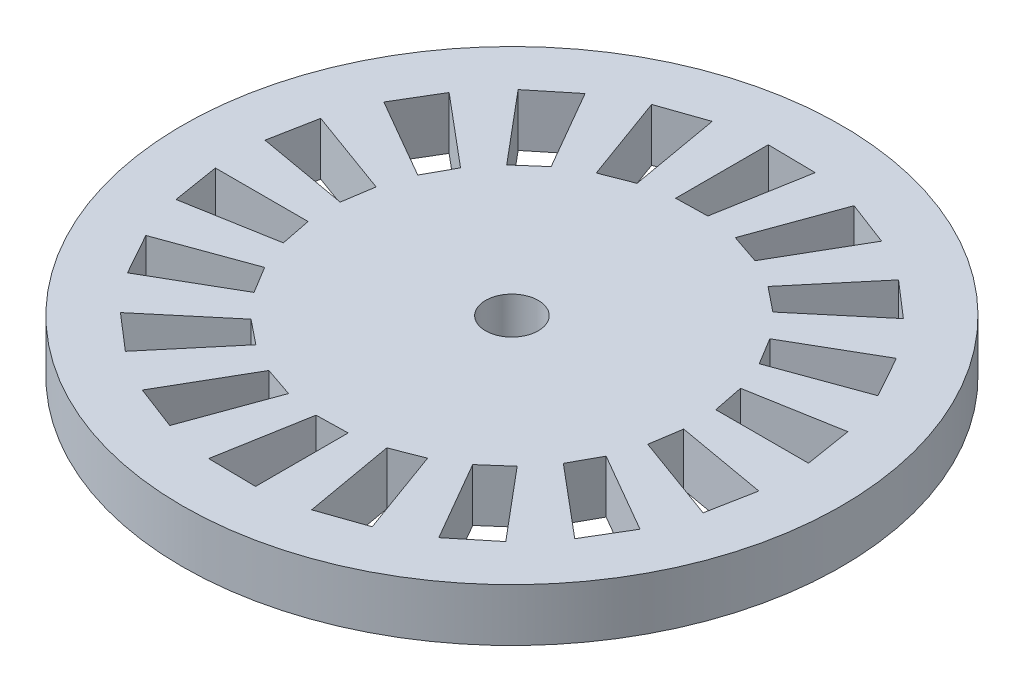
SolidWorks part; units mm, degrees
ref_plane "Front Plane" through (0, 0, 0) normal (0, 0, 1) x (1, 0, 0)
ref_plane "Top Plane" through (0, 0, 0) normal (0, 1, 0) x (1, 0, 0)
ref_plane "Right Plane" through (0, 0, 0) normal (1, 0, 0) x (0, 0, -1)
sketch "스케치1" plane through (0, 0, 0) normal (0, 1, 0) x (1, 0, 0)
  circle A0 centre (0, 0) radius 12.5
extrude "보스-돌출1" add sketch "스케치1" along normal blind 2
sketch "스케치2" plane through (0, 2, 0) normal (0, 1, 0) x (1, 0, 0)
  line L0 (0, 0) -> (0, 50000) construction
  line L1 (0, 0) -> (50000, 0) construction
  line L2 (-0.75, 2.803) -> (-0.75, 50002.803) construction
  line L3 (1.2949, 11.8069) -> (8683.7038, 49252.1946) construction
  line L4 (0.0775, 0.4397) -> (8682.4864, 49240.8273) construction
  line L5 (-0.75, 6.9597) -> (0.4448, 6.9859)
  line L6 (0.4448, 6.9859) -> (1.0551, 10.4469)
  line L7 (1.0551, 10.4469) -> (-0.75, 10.4732)
  line L8 (-0.75, 10.4732) -> (-0.75, 6.9597)
  circle A0 centre (0, 0) radius 7 construction
  circle A1 centre (0, 0) radius 10.5 construction
  dimension "D3" = 14
  dimension "D4" = 21
  dimension "D1" = 0.75
  dimension "D2" = 10
  dimension "D5" = 0.775
extrude "컷-돌출1" cut sketch "스케치2" against normal blind 2
sketch "스케치3" plane through (0, 2, 0) normal (0, 1, 0) x (1, 0, 0)
  circle A0 centre (0, 0) radius 1
extrude "컷-돌출2" cut sketch "스케치3" against normal blind 22
sketch "스케치4" plane through (0, 2, 0) normal (0, 1, 0) x (1, 0, 0)
  circle A0 centre (0, 0) radius 2
extrude "보스-돌출2" add sketch "스케치4" against normal blind 3 from surface starting at face at (0, 0, 1)
pattern_circular "원형 패턴1" count 18 every 20 about axis through (0, -20, 0) along (0, 1, 0) of "컷-돌출1"
sketch "스케치5" plane through (0, 2, 0) normal (0, 1, 0) x (1, 0, 0)
  circle A0 centre (0, 0) radius 1
extrude "컷-돌출3" cut sketch "스케치5" against normal blind 23
